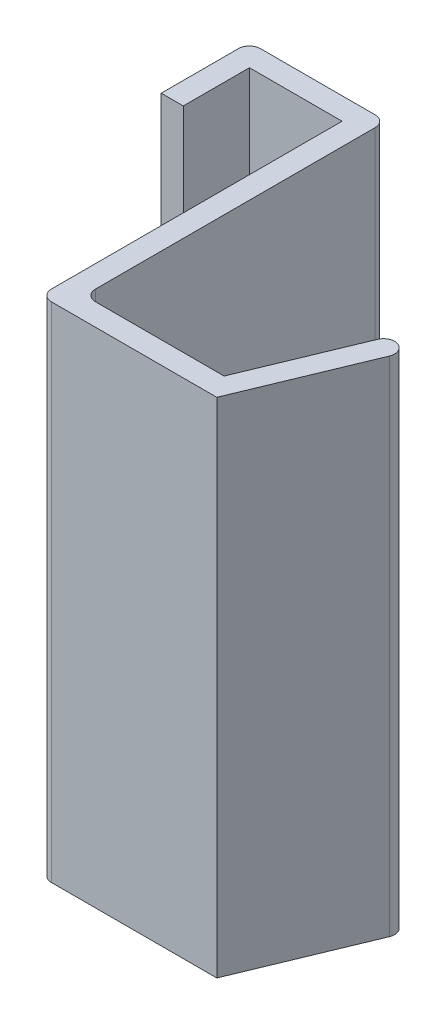
SolidWorks part; units mm, degrees
ref_plane "Front Plane" through (0, 0, 0) normal (0, 0, 1) x (1, 0, 0)
ref_plane "Top Plane" through (0, 0, 0) normal (0, 1, 0) x (1, 0, 0)
ref_plane "Right Plane" through (0, 0, 0) normal (1, 0, 0) x (0, 0, -1)
sketch "ｽｹｯﾁ1" plane through (0, 0, 0) normal (0, 1, 0) x (1, 0, 0)
  line L0 (40, -36.7) -> (52.4264, -6.7)
  line L21 (40, -36.7) -> (35.3806, -34.7866)
  line L22 (52.4264, -6.7) -> (47.807, -4.7866)
  line L23 (35.3806, -34.7866) -> (47.807, -4.7866)
  line L24 (52.4264, -6.7) -> (12.0684, -6.7) construction
  line L25 (47.807, -4.7866) -> (36.2626, -32.6571) construction
  line L26 (40, -36.7) -> (40, -14.7866) construction
  line L32 (0, -31.7) -> (5, -31.7)
  line L33 (0, -31.7) -> (0, 36.7)
  line L34 (0, 36.7) -> (5, 36.7)
  line L35 (5, -31.7) -> (5, 36.7)
  line L36 (0, 36.7) -> (-21, 36.7)
  line L37 (0, 36.7) -> (0, 31.7)
  line L38 (0, 31.7) -> (-21, 31.7)
  line L39 (-21, 36.7) -> (-21, 31.7)
  line L40 (-21, 36.7) -> (-26, 36.7)
  line L41 (-21, 36.7) -> (-21, 16.7)
  line L42 (-21, 16.7) -> (-26, 16.7)
  line L43 (-26, 36.7) -> (-26, 16.7)
  line L44 (0, -31.7) -> (40, -31.7)
  line L45 (0, -31.7) -> (0, -36.7)
  line L46 (0, -36.7) -> (40, -36.7)
  line L47 (40, -31.7) -> (40, -36.7)
  line L51 (35.1804, -36.7) -> (46.742, -36.7) construction
  point P15 (40, -6.7)
  dimension "D2" = 5
  dimension "D3" = 5
  dimension "D4" = 20
  dimension "D5" = 5
  dimension "D6" = 21
  dimension "D7" = 40
  dimension "D8" = 67.5
  dimension "D9" = 5
  dimension "D11" = 30
  dimension "D12" = 68.4
  dimension "D13" = 5
extrude "ﾎﾞｽ - 押し出し1" add sketch "ｽｹｯﾁ1" along normal blind 114 contours L23 L0 L22 | L21 L23 | L40 | L34 | L23 L21 | L40 L42 | L40 | L37 L36 L39 L38 region at (44.5672, 0, 19.2366) region at (18.349, 0, 34.2291) region at (38.1165, 0, 33.8811) region at (2.5, 0, -2.5) region at (-23.5, 0, -26.7)
fillet "ﾌｨﾚｯﾄ5" radius 2.5 1 edges at (-26, 57, -36.7)
fillet "ﾌｨﾚｯﾄ6" radius 2.5 1 edges at (5, 57, -36.7)
fillet "ﾌｨﾚｯﾄ8" radius 2.5 2 edges at (52.4264, 57, 6.7) (47.807, 57, 4.7866)
fillet "ﾌｨﾚｯﾄ10" radius 2.5 1 edges at (0, 57, 36.7)
fillet "ﾌｨﾚｯﾄ11" radius 2.5 1 edges at (5, 57, 31.7)
